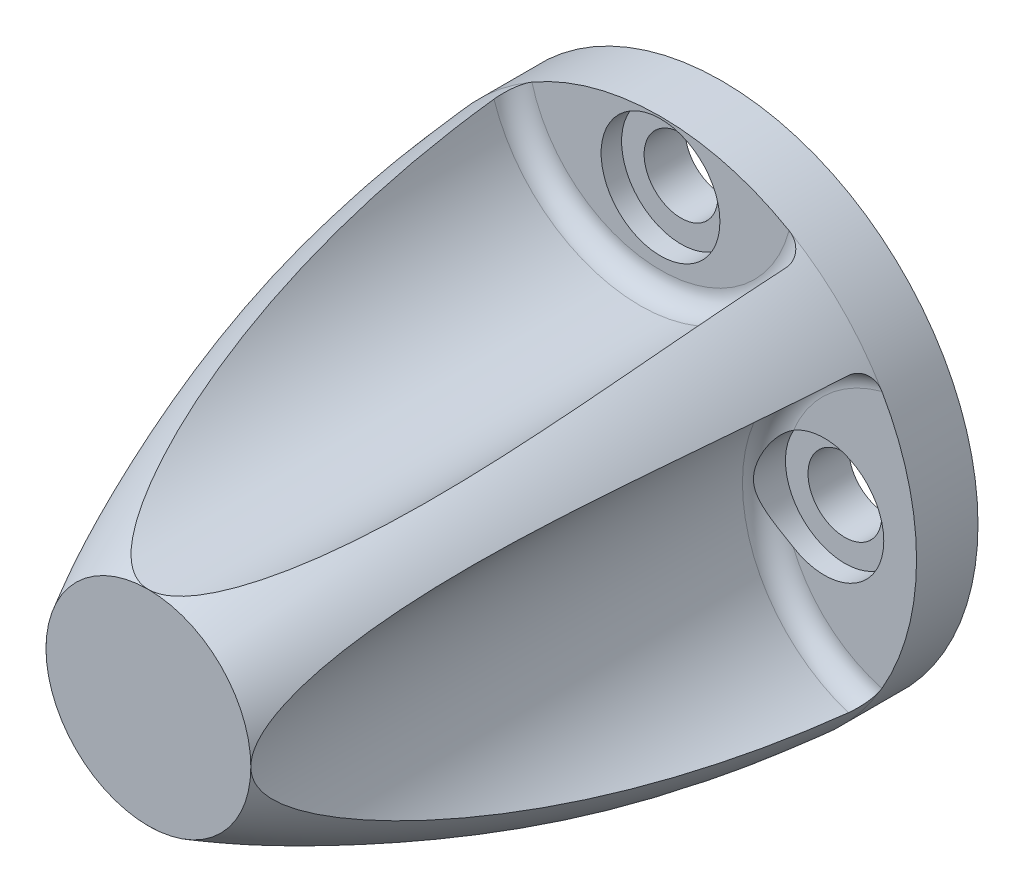
SolidWorks part; units mm, degrees
material "Rubber"
ref_plane "Front Plane" through (0, 0, 0) normal (0, 0, 1) x (1, 0, 0)
ref_plane "Top Plane" through (0, 0, 0) normal (0, 1, 0) x (1, 0, 0)
ref_plane "Right Plane" through (0, 0, 0) normal (1, 0, 0) x (0, 0, -1)
sketch "Sketch1" plane through (0, 0, 0) normal (0, 0, 1) x (1, 0, 0)
  circle A0 centre (0, 0) radius 12.5
  dimension "D1" = 25
extrude "Boss-Extrude1" add sketch "Sketch1" along normal blind 3
sketch "Sketch2" plane through (0, 0, 3) normal (0, 0, 1) x (1, 0, 0)
  circle A0 centre (0, 0) radius 9.5 construction
  circle A1 centre (0, 0) radius 8 construction
  circle A2 centre (0, 9.5) radius 1.8
  circle A3 centre (0, -9.5) radius 1.8
  circle A4 centre (8, 0) radius 1.8
  circle A5 centre (-8, 0) radius 1.8
  dimension "D1" = 19
  dimension "D2" = 16
  dimension "D3" = 3.6
extrude "Cut-Extrude1" cut sketch "Sketch2" against normal through all
sketch "Sketch3" plane through (0, 0, 3) normal (0, 0, 1) x (1, 0, 0)
  arc A0 (-7.1545, 10.25) -> (7.1545, 10.25) centre (0, 12.5) ccw
  circle A1 centre (0, 0) radius 12.5 construction
  arc A2 (10.25, 7.1545) -> (10.25, -7.1545) centre (12.5, 0) ccw
  arc A3 (7.1545, -10.25) -> (-7.1545, -10.25) centre (0, -12.5) ccw
  arc A4 (-10.25, -7.1545) -> (-10.25, 7.1545) centre (-12.5, 0) ccw
  arc A5 (10.25, 7.1545) -> (7.1545, 10.25) centre (0, 0) ccw
  circle A6 centre (0, 0) radius 12.5
  arc A7 (7.1545, -10.25) -> (10.25, -7.1545) centre (0, 0) ccw
  arc A8 (-7.1545, 10.25) -> (-10.25, 7.1545) centre (0, 0) ccw
  arc A9 (-10.25, -7.1545) -> (-7.1545, -10.25) centre (0, 0) ccw
  point P4 (0, 0)
  point P6 (0, 0)
  point P7 (0, 0)
  point P14 (0, 0)
  dimension "D1" = 15
  dimension "D3" = 17.6777
  dimension "D4" = 0
  dimension "D2" = 4
extrude "Boss-Extrude2" add sketch "Sketch3" along normal blind 25 contours A7 A2 A5 A0 A8 A4 A9 A3
sketch "Sketch5" plane through (0, 0, 0) normal (0, 1, 0) x (1, 0, 0)
  line L0 (10.25, -28) -> (10.25, -3) construction
  line L1 (-7.1545, -28) -> (7.1545, -28) construction
  line L2 (12.5, -3) -> (12.5, -28)
  line L3 (12.5, -28) -> (5, -28)
  line L4 (0, -28) -> (0, -7.44) construction
  spline S0 degree 2 poles (12.5, -3) (11.5082, -16.3167) (5, -28) knots 0 0 0 1 1 1
  dimension "D1" = 5
revolve "Cut-Revolve2" cut sketch "Sketch5" angle 360 about L4
sketch "Sketch6" plane through (0, 0, 0) normal (0, 0, -1) x (-1, 0, 0)
  circle A0 centre (0, 0) radius 3
  dimension "D1" = 6
extrude "Cut-Extrude2" cut sketch "Sketch6" against normal blind 5
fillet "Fillet1" radius 1 4 edges at (0, 5, 3) (5, 0, 3) (0, -5, 3) (-5, 0, 3)
sketch "Sketch7" plane through (0, 0, 3) normal (0, 0, 1) x (1, 0, 0)
  circle A0 centre (0, 9.5) radius 2.9
  circle A1 centre (8, 0) radius 2.9
  circle A2 centre (0, -9.5) radius 2.9
  circle A3 centre (-8, 0) radius 2.9
  dimension "D1" = 5.8
extrude "Cut-Extrude3" cut sketch "Sketch7" against normal blind 1 and the other way through all
